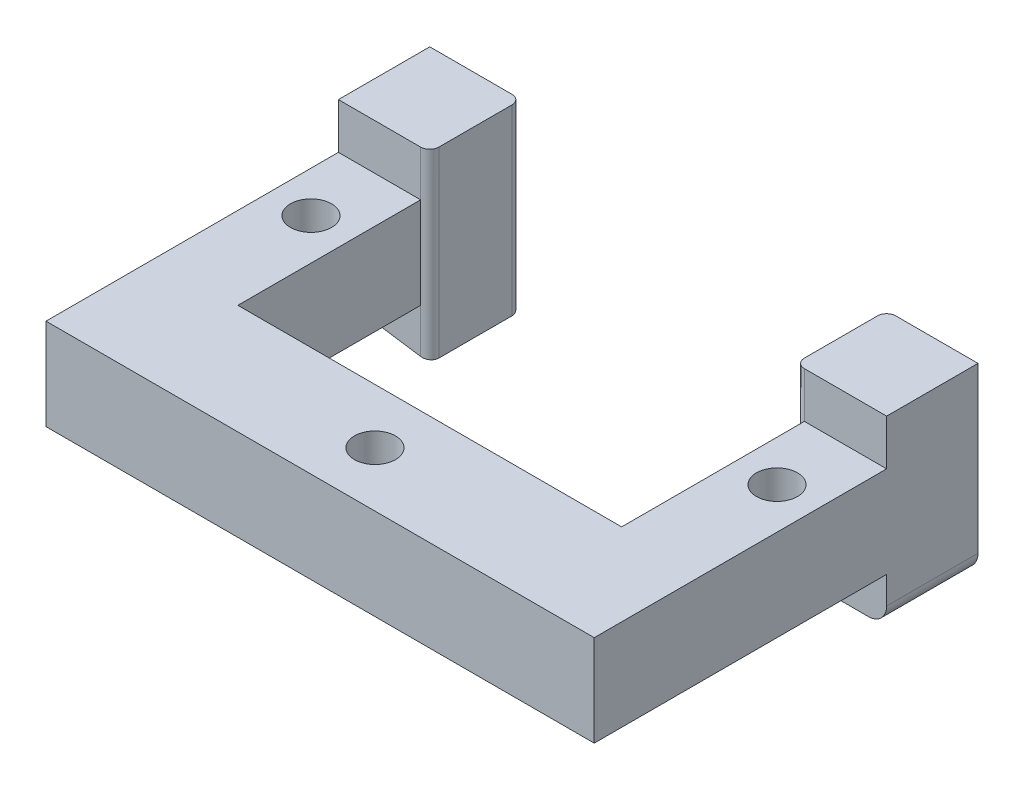
SolidWorks part; units mm, degrees
material "ABS"
ref_plane "Front Plane" through (0, 0, 0) normal (0, 0, 1) x (1, 0, 0)
ref_plane "Top Plane" through (0, 0, 0) normal (0, 1, 0) x (1, 0, 0)
ref_plane "Right Plane" through (0, 0, 0) normal (1, 0, 0) x (0, 0, -1)
sketch "Sketch1" plane through (0, 0, 0) normal (0, 1, 0) x (1, 0, 0)
  line L0 (0, 30.876) -> (0, -57.2152) construction
  line L1 (-20, 0) -> (-30, 0)
  line L2 (-30, 0) -> (-30, -42)
  line L3 (-30, -42) -> (30, -42)
  line L4 (30, -42) -> (30, 0)
  line L5 (30, 0) -> (20, 0)
  line L6 (20, 0) -> (20, -10)
  line L7 (20, -30) -> (-20, -30)
  line L8 (-20, -10) -> (-20, 0)
  line L9 (-20, -10) -> (-21, -10)
  line L10 (-21, -10) -> (-21, -30)
  line L11 (-21, -30) -> (-20, -30)
  line L12 (21, -30) -> (20, -30)
  line L13 (20, -10) -> (21, -10)
  line L14 (21, -10) -> (21, -30)
  point P5 (-25, 0)
  dimension "D1" = 40
  dimension "D2" = 10
  dimension "D3" = 30
  dimension "D4" = 12
  dimension "D5" = 10
  dimension "D6" = 1
extrude "Boss-Extrude1" add sketch "Sketch1" along normal blind 20
sketch "Sketch2" plane through (0, 0, 0) normal (0, 0, -1) x (-1, 0, 0)
  line L0 (-25, 20) -> (-25, 0) construction
  line L1 (-30, 20) -> (-20, 20) construction
  line L2 (-30, 0) -> (-20, 0) construction
  line L4 (0, 0) -> (0, 42.0055) construction
  circle A2 centre (-24.25, 14.79) radius 2.75
  circle A3 centre (-24.25, 4.79) radius 2.75
  point P6 (-24.25, 14.79)
  point P11 (-24.25, 4.79)
  dimension "D4" = 5.5
  dimension "D1" = 5.21
  dimension "D2" = 24.25
  dimension "D3" = 15.21
extrude "Cut-Extrude1" cut sketch "Sketch2" against normal blind 8
mirror "Mirror1" about plane through (0, 0, 0) normal (1, 0, 0) of "Cut-Extrude1"
fillet "Fillet1" radius 1 4 edges at (-20, 10, 0) (20, 10, 0) (20, 10, 10) (-20, 10, 10)
sketch "Sketch7" plane through (0, 0, 0) normal (0, -1, 0) x (1, 0, 0)
  line L0 (-21, 10) -> (-30, 10)
  line L1 (21, 10) -> (30, 10)
  line L10 (21, 30) -> (21, 10)
  line L11 (20, 9) -> (20, 1)
  line L12 (21, 0) -> (30, 0)
  line L13 (30, 0) -> (30, 42)
  line L14 (30, 42) -> (-30, 42)
  line L15 (-30, 42) -> (-30, 0)
  line L16 (-30, 0) -> (-21, 0)
  line L17 (-20, 1) -> (-20, 9)
  line L18 (-21, 10) -> (-21, 30)
  line L19 (-21, 30) -> (21, 30)
  line L20 (21, 30) -> (21, 10)
  line L21 (20, 9) -> (20, 1)
  line L22 (21, 0) -> (30, 0)
  line L23 (30, 0) -> (30, 42)
  line L24 (30, 42) -> (-30, 42)
  line L25 (-30, 42) -> (-30, 0)
  line L26 (-30, 0) -> (-21, 0)
  line L27 (-20, 1) -> (-20, 9)
  line L28 (-21, 10) -> (-21, 30)
  line L29 (-21, 30) -> (21, 30)
  arc A4 (21, 10) -> (20, 9) centre (21, 9) ccw
  arc A5 (20, 1) -> (21, 0) centre (21, 1) ccw
  arc A6 (-21, 0) -> (-20, 1) centre (-21, 1) ccw
  arc A7 (-20, 9) -> (-21, 10) centre (-21, 9) ccw
  arc A8 (21, 10) -> (20, 9) centre (21, 9) ccw
  arc A9 (20, 1) -> (21, 0) centre (21, 1) ccw
  arc A10 (-21, 0) -> (-20, 1) centre (-21, 1) ccw
  arc A11 (-20, 9) -> (-21, 10) centre (-21, 9) ccw
  line M15 (21, 30) -> (21, 10)
  line M20 (30, 0) -> (30, 42)
  line M21 (30, 42) -> (-30, 42)
  line M22 (-30, 42) -> (-30, 0)
  line M27 (-21, 10) -> (-21, 30)
  line M28 (-21, 30) -> (21, 30)
  dimension "D1" = 0
extrude "Cut-Extrude3" cut sketch "Sketch7" against normal blind 5 contours L1 L0 M15 M20 M21 M22 M27 M28 region at (0, 0, 30.6667)
ref_plane "Plane2" through (0, 10, 0) normal (0, 1, 0) x (1, 0, 0)
mirror "Mirror2" about plane through (0, 10, 0) normal (0, 1, 0) of "Cut-Extrude3"
sketch "Sketch8" plane through (0, 15, 0) normal (0, 1, 0) x (1, 0, 0)
  line L8 (21, -10) -> (21, -30)
  line L9 (21, -30) -> (-21, -30)
  line L10 (-21, -30) -> (-21, -10)
  line L11 (-21, -10) -> (-30, -10)
  line L12 (-30, -10) -> (-30, -42)
  line L13 (-30, -42) -> (30, -42)
  line L14 (30, -42) -> (30, -10)
  line L15 (30, -10) -> (21, -10)
  line L16 (21, -10) -> (21, -30)
  line L17 (21, -30) -> (-21, -30)
  line L18 (-21, -30) -> (-21, -10)
  line L19 (-21, -10) -> (-30, -10)
  line L20 (-30, -10) -> (-30, -42)
  line L21 (-30, -42) -> (30, -42)
  line L22 (30, -42) -> (30, -10)
  line L23 (30, -10) -> (21, -10)
  dimension "D1" = 0
sketch "Sketch9" plane through (0, 5, 0) normal (0, -1, 0) x (1, 0, 0)
  line L0 (-30, 36) -> (30, 36) construction
  line L1 (-25.5, 10) -> (-25.5, 42) construction
  line L2 (0, 51.8317) -> (0, -8.1141) construction
  line L8 (21, 30) -> (21, 10)
  line L9 (21, 10) -> (30, 10)
  line L10 (30, 10) -> (30, 42)
  line L11 (30, 42) -> (-30, 42)
  line L12 (-30, 42) -> (-30, 10)
  line L13 (-30, 10) -> (-21, 10)
  line L14 (-21, 10) -> (-21, 30)
  line L15 (-21, 30) -> (21, 30)
  line L16 (21, 30) -> (21, 10)
  line L17 (21, 10) -> (30, 10)
  line L18 (30, 10) -> (30, 42)
  line L19 (30, 42) -> (-30, 42)
  line L21 (-30, 10) -> (-21, 10)
  line L23 (-21, 30) -> (21, 30)
  circle A0 centre (0, 36) radius 2.25
  circle A1 centre (-25.5, 17.5) radius 2.25
  circle A2 centre (25.5, 17.5) radius 2.25
  dimension "D2" = 4.5
  dimension "D3" = 7.5
  dimension "D1" = 0
extrude "Cut-Extrude5" cut sketch "Sketch9" against normal through all contours A1 | A2 | A0 region at (-25.5, 5, 17.5) region at (25.5, 5, 17.5)
chamfer "Chamfer1" distance 10 distance2 1.5 1 edges at (-30, 0, 5) first distance on face at (-23.5976, 0, 5)
fillet "Fillet2" radius 2 2 edges at (-30, 1.5, 5) (30, 0, 5)
